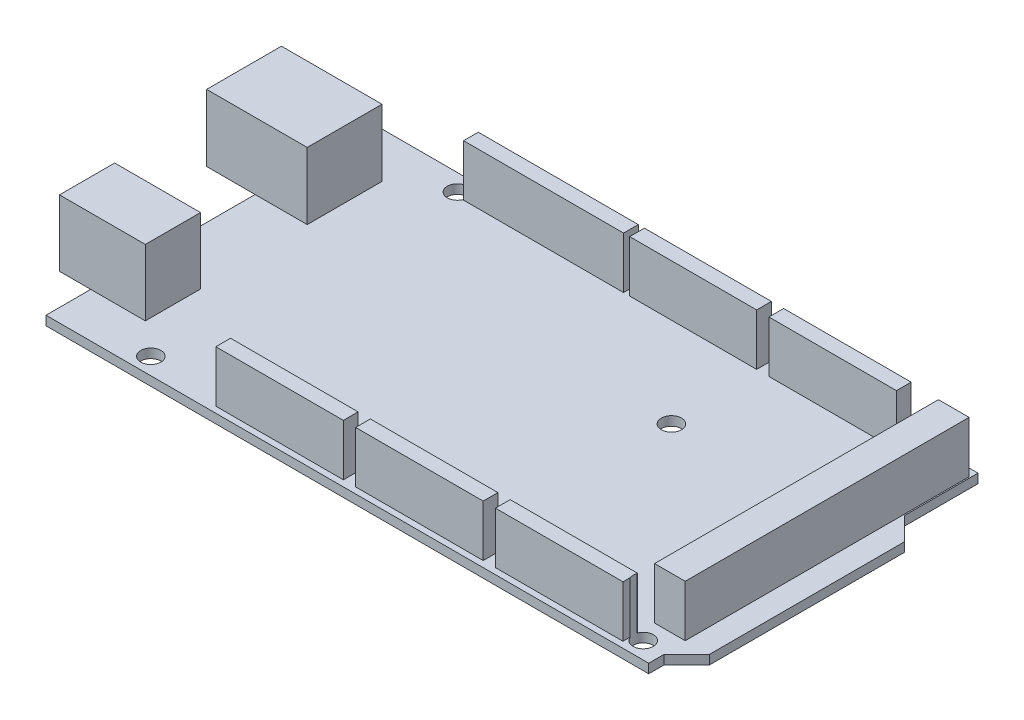
SolidWorks part; units mm, degrees
ref_plane "Спереди" through (0, 0, 0) normal (0, 0, 1) x (1, 0, 0)
ref_plane "Сверху" through (0, 0, 0) normal (0, 1, 0) x (1, 0, 0)
ref_plane "Справа" through (0, 0, 0) normal (1, 0, 0) x (0, 0, -1)
sketch "Эскиз2" plane through (0, 0, 0) normal (0, 1, 0) x (1, 0, 0)
  line L1 (-53.939, 27.4881) -> (48.061, 27.4881)
  line L2 (-53.939, 27.4881) -> (-53.939, -26.2119)
  line L3 (-53.939, -26.2119) -> (48.061, -26.2119)
  line L4 (48.061, 27.4881) -> (48.061, -26.2119)
  dimension "D1" = 102
  dimension "D2" = 53.7
extrude "Бобышка-Вытянуть1" add sketch "Эскиз2" along normal blind 1.5
sketch "Эскиз3" plane through (0, 1.5, 0) normal (0, 1, 0) x (1, 0, 0)
  line L0 (48.061, 27.4881) -> (-53.939, 27.4881) construction
  line L1 (-45.439, 7.8881) -> (-61.839, 7.8881)
  line L2 (-45.439, 7.8881) -> (-45.439, 20.0881)
  line L3 (-45.439, 20.0881) -> (-61.839, 20.0881)
  line L4 (-61.839, 7.8881) -> (-61.839, 20.0881)
  line L5 (-45.439, 7.8881) -> (-61.839, 20.0881) construction
  line L6 (-45.439, 20.0881) -> (-61.839, 7.8881) construction
  line L7 (-53.939, 27.4881) -> (-53.939, -26.2119) construction
  point P0 (-53.639, 13.9881)
  dimension "D1" = 7.4
  dimension "D2" = 7.9
  dimension "D3" = 12.2
  dimension "D4" = 16.4
extrude "Бобышка-Вытянуть2" add sketch "Эскиз3" along normal blind 10.9
sketch "Эскиз5" plane through (0, 1.5, 0) normal (0, 1, 0) x (1, 0, 0)
  line L0 (-53.939, -26.2119) -> (48.061, -26.2119) construction
  line L1 (-45.039, -18.9119) -> (-59.039, -18.9119)
  line L2 (-45.039, -18.9119) -> (-45.039, -9.9119)
  line L3 (-45.039, -9.9119) -> (-59.039, -9.9119)
  line L4 (-59.039, -18.9119) -> (-59.039, -9.9119)
  line L5 (-45.039, -18.9119) -> (-59.039, -9.9119) construction
  line L6 (-45.039, -9.9119) -> (-59.039, -18.9119) construction
  line L8 (-53.939, 7.8881) -> (-53.939, -26.2119) construction
  point P0 (-52.039, -14.4119)
  dimension "D1" = 14
  dimension "D2" = 9
  dimension "D3" = 7.3
  dimension "D4" = 5.1
extrude "Бобышка-Вытянуть3" add sketch "Эскиз5" along normal blind 10.8
sketch "Эскиз6" plane through (0, 1.5, 0) normal (0, 1, 0) x (1, 0, 0)
  line L0 (-53.939, -18.9119) -> (-53.939, -26.2119) construction
  line L1 (-6.439, -25.2119) -> (-27.239, -25.2119)
  line L2 (-6.439, -25.2119) -> (-6.439, -22.8119)
  line L3 (-6.439, -22.8119) -> (-27.239, -22.8119)
  line L4 (-27.239, -25.2119) -> (-27.239, -22.8119)
  line L5 (-6.439, -25.2119) -> (-27.239, -22.8119) construction
  line L6 (-6.439, -22.8119) -> (-27.239, -25.2119) construction
  line L7 (-53.939, -26.2119) -> (48.061, -26.2119) construction
  line L8 (48.061, 27.4881) -> (-53.939, 27.4881) construction
  line L9 (-4.439, -22.8119) -> (16.361, -22.8119)
  line L10 (-4.439, -22.8119) -> (-4.439, -25.2119)
  line L11 (-4.439, -25.2119) -> (16.361, -25.2119)
  line L12 (16.361, -22.8119) -> (16.361, -25.2119)
  line L13 (18.361, -22.8119) -> (39.161, -22.8119)
  line L14 (18.361, -22.8119) -> (18.361, -25.2119)
  line L15 (18.361, -25.2119) -> (39.161, -25.2119)
  line L16 (39.161, -22.8119) -> (39.161, -25.2119)
  line L17 (-36.139, 26.4881) -> (-10.039, 26.4881)
  line L18 (-36.139, 26.4881) -> (-36.139, 24.0881)
  line L19 (-36.139, 24.0881) -> (-10.039, 24.0881)
  line L20 (-10.039, 26.4881) -> (-10.039, 24.0881)
  line L21 (-53.939, 27.4881) -> (-53.939, 20.0881) construction
  line L22 (48.061, -26.2119) -> (48.061, 27.4881) construction
  line L23 (-9.039, 26.4881) -> (11.661, 26.4881)
  line L24 (-9.039, 26.4881) -> (-9.039, 24.0881)
  line L25 (-9.039, 24.0881) -> (11.661, 24.0881)
  line L26 (11.661, 26.4881) -> (11.661, 24.0881)
  line L27 (13.661, 26.4881) -> (34.461, 26.4881)
  line L28 (13.661, 26.4881) -> (13.661, 24.0881)
  line L29 (13.661, 24.0881) -> (34.461, 24.0881)
  line L30 (34.461, 26.4881) -> (34.461, 24.0881)
  line L31 (44.161, 26.2381) -> (39.161, 26.2381)
  line L32 (44.161, 26.2381) -> (44.161, -20.0619)
  line L33 (44.161, -20.0619) -> (39.161, -20.0619)
  line L34 (39.161, 26.2381) -> (39.161, -20.0619)
  point P0 (-16.839, -24.0119)
  point P25 (-53.939, 23.7881)
  dimension "D1" = 20.8
  dimension "D2" = 2.4
  dimension "D3" = 26.7
  dimension "D4" = 1
  dimension "D5" = 2
  dimension "D6" = 20.8
  dimension "D7" = 2
  dimension "D8" = 20.8
  dimension "D9" = 2.4
  dimension "D10" = 26.1
  dimension "D11" = 1
  dimension "D12" = 17.8
  dimension "D13" = 1
  dimension "D14" = 2
  dimension "D15" = 20.7
  dimension "D16" = 20.8
  dimension "D17" = 5
  dimension "D18" = 1.25
  dimension "D19" = 46.3
  dimension "D20" = 3.9
extrude "Бобышка-Вытянуть6" add sketch "Эскиз6" along normal blind 8.4
sketch "Эскиз9" plane through (0, 1.5, 0) normal (0, 1, 0) x (1, 0, 0)
  line L0 (48.061, -26.2119) -> (48.061, 27.4881) construction
  line L1 (48.061, 27.4881) -> (44.361, 27.4881)
  line L2 (48.061, 27.4881) -> (48.061, 15.4881)
  line L3 (48.061, 15.4881) -> (44.361, 15.4881)
  line L4 (44.361, 27.4881) -> (44.361, 15.4881)
  line L5 (48.061, -26.2119) -> (44.361, -26.2119)
  line L6 (48.061, -26.2119) -> (48.061, -23.7119)
  line L7 (48.061, -23.7119) -> (44.361, -23.7119)
  line L8 (44.361, -26.2119) -> (44.361, -23.7119)
  line L9 (-53.939, -26.2119) -> (48.061, -26.2119) construction
  dimension "D1" = 3.7
  dimension "D2" = 12
  dimension "D3" = 3.7
  dimension "D4" = 2.5
extrude "Вырез-Вытянуть1" cut sketch "Эскиз9" against normal through all
chamfer "Фаска1" distance 3.7 angle 45 2 edges at (48.061, 0.75, 23.7119) (48.061, 0.75, -15.4881)
sketch "Эскиз7" plane through (0, 1.5, 0) normal (0, 1, 0) x (1, 0, 0)
  line L0 (-36.139, 26.4881) -> (-36.139, 24.0881) construction
  line L1 (44.361, 27.4881) -> (-53.939, 27.4881) construction
  line L2 (-53.939, -26.2119) -> (44.361, -26.2119) construction
  line L3 (-53.939, -18.9119) -> (-53.939, -26.2119) construction
  line L5 (44.361, -23.7119) -> (44.361, -26.2119) construction
  line L6 (44.361, 27.4881) -> (44.361, 15.4881) construction
  line L7 (48.061, -20.0119) -> (48.061, 11.7881) construction
  line L8 (44.361, 27.4881) -> (-53.939, 27.4881) construction
  line L9 (-53.939, -26.2119) -> (44.361, -26.2119) construction
  circle A0 centre (-37.789, 24.7381) radius 1.65
  circle A1 centre (-39.589, -23.4619) radius 1.65
  circle A2 centre (12.411, 9.4381) radius 1.65
  circle A3 centre (12.411, -18.7019) radius 1.65
  circle A4 centre (36.551, 24.7381) radius 1.65
  circle A5 centre (40.711, -23.4619) radius 1.65
  dimension "D1" = 3.3
  dimension "D2" = 2.75
  dimension "D3" = 2.75
  dimension "D4" = 2.75
  dimension "D5" = 2.75
  dimension "D6" = 14.35
  dimension "D7" = 3.65
  dimension "D8" = 7.81
  dimension "D9" = 35.65
  dimension "D10" = 18.05
  dimension "D11" = 7.51
extrude "Вырез-Вытянуть2" cut sketch "Эскиз7" against normal through all both and the other way through all
